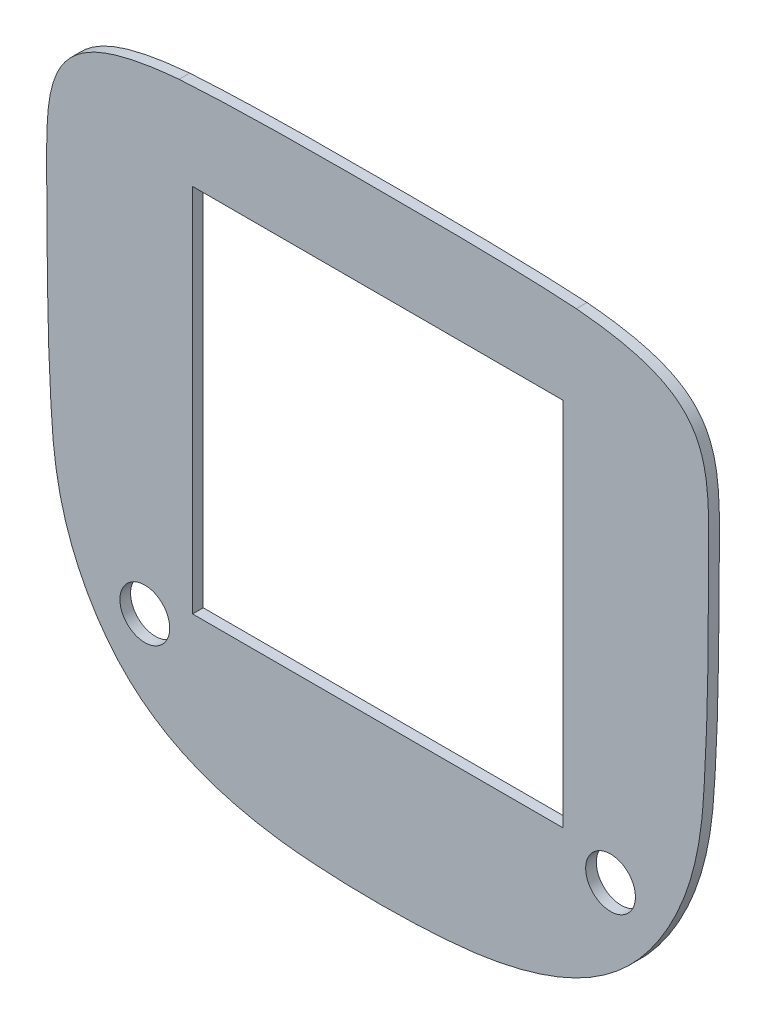
SolidWorks part; units mm, degrees
ref_plane "Front Plane" through (0, 0, 0) normal (0, 0, 1) x (1, 0, 0)
ref_plane "Top Plane" through (0, 0, 0) normal (0, 1, 0) x (1, 0, 0)
ref_plane "Right Plane" through (0, 0, 0) normal (1, 0, 0) x (0, 0, -1)
ref_plane "Plane1" through (0, 0, 100) normal (0, 0, -1) x (-1, 0, 0)
sketch "Sketch1" plane through (0, 0, 100) normal (0, 0, -1) x (-1, 0, 0)
  line L0 (0, 109.7056) -> (0, -73.1371) construction
  line L2 (-52.07, 79.9412) -> (52.07, 79.9412)
  line L3 (-52.07, 79.9412) -> (-52.07, -24.1988)
  line L4 (-52.07, -24.1988) -> (52.07, -24.1988)
  line L5 (52.07, 79.9412) -> (52.07, -24.1988)
  line L6 (-52.07, 79.9412) -> (52.07, -24.1988) construction
  line L7 (-52.07, -24.1988) -> (52.07, 79.9412) construction
  circle A0 centre (-65.5, -30.8878) radius 7
  circle A1 centre (65.5, -30.8878) radius 7
  spline S0 degree 3 poles (431.5804, 2885.9654) (340.7707, 127.7819) (179.6832, -59.6034) (9.156, -68.4596) (4.5994, -68.5614) (-4.5192, -68.5626) (-9.0812, -68.4622) (-15.9299, -68.1084) (-18.2137, -67.9563) (-163.7651, -55.7203) (-324.0036, 115.5461) (2276.1505, 1823.2174) knots -8.863763 -8.863763 -8.863763 -8.863763 0.25 0.25 0.5 0.5 0.75 0.75 0.875 0.875 8.712653 8.712653 8.712653 8.712653 only from (27.355, -67.0609) to (-27.355, -67.0609)
  spline S1 degree 3 poles (-380.9572, -2850.4105) (-413.6013, 4.6753) (-231.265, 98.3934) (-37.5468, 104.943) (-32.9585, 105.0458) (-23.7809, 105.1902) (-19.1919, 105.2316) (-10.0136, 105.2808) (-5.2092, 105.2889) (-0.4047, 105.2894) (-0.1179, 105.2895) (-0.0476, 105.2895) (2.0953, 105.2894) (4.1642, 105.2881) (8.5976, 105.2806) (10.962, 105.2737) (18.055, 105.2405) (22.7834, 105.2016) (32.2392, 105.0607) (36.9665, 104.959) (231.9135, 98.5111) (424.3413, 5.167) (-68.9115, -2862.1998) knots -5.033027 -5.033027 -5.033027 -5.033027 0.125 0.125 0.25 0.25 0.375 0.375 0.5 0.505859 0.505859 0.507813 0.507813 0.5625 0.5625 0.625 0.625 0.75 0.75 0.875 0.875 5.905743 5.905743 5.905743 5.905743 only from (-55.8659, 104.1312) to (55.8659, 104.1312)
  spline S2 degree 3 poles (-55.8659, 104.1312) (-51.2933, 104.4268) (-46.7138, 104.633) (-37.5468, 104.943) (-32.9585, 105.0458) (-23.7809, 105.1902) (-19.1919, 105.2316) (-10.0136, 105.2808) (-5.2092, 105.2889) (-0.4047, 105.2894) (-0.1179, 105.2895) (-0.0476, 105.2895) (2.0953, 105.2894) (4.1642, 105.2881) (8.5976, 105.2806) (10.962, 105.2737) (18.055, 105.2405) (22.7834, 105.2016) (32.2392, 105.0607) (36.9665, 104.959) (46.4194, 104.6463) (51.1472, 104.4362) (55.8659, 104.1312) knots 0 0 0 0 0.125 0.125 0.25 0.25 0.375 0.375 0.5 0.505859 0.505859 0.507813 0.507813 0.5625 0.5625 0.625 0.625 0.75 0.75 0.875 0.875 1 1 1 1
  spline S3 degree 3 poles (27.355, -67.0609) (22.8108, -67.6157) (18.2617, -67.9867) (9.156, -68.4596) (4.5994, -68.5614) (-4.5192, -68.5626) (-9.0812, -68.4622) (-15.9299, -68.1084) (-18.2137, -67.9563) (-22.7835, -67.5721) (-25.0727, -67.3396) (-27.355, -67.0609) knots 0 0 0 0 0.25 0.25 0.5 0.5 0.75 0.75 0.875 0.875 1 1 1 1
  spline S5 degree 3 poles (167.7953, 3089.1539) (-201.0636, -49.2885) (-54.5587, 119.9031) (65.3699, 102.9931) (67.7267, 102.5852) (71.2329, 101.7869) (72.3966, 101.489) (74.7111, 100.8094) (75.8628, 100.4275) (78.1118, 99.5645) (79.2128, 99.082) (80.8185, 98.2584) (81.3461, 97.9672) (82.3838, 97.347) (82.8958, 97.0168) (84.3811, 95.975) (85.3075, 95.2102) (86.5865, 93.9414) (86.9943, 93.4982) (87.7711, 92.5688) (88.1403, 92.0818) (89.1658, 90.5883) (89.7485, 89.5389) (90.4902, 87.8946) (90.7155, 87.3349) (91.1265, 86.1944) (91.3113, 85.616) (91.8065, 83.8785) (92.0608, 82.7092) (92.467, 80.3557) (92.6189, 79.1716) (92.8517, 76.7929) (92.9326, 75.5984) (93.05, 73.203) (93.0856, 72.0013) (93.127, 69.5995) (93.1345, 68.3986) (93.1287, 65.997) (93.118, 64.7962) (93.0925, 61.1938) (93.0791, 58.7922) (93.037, 51.5874) (93.0085, 46.7842) (92.8583, 32.3749) (92.6764, 22.7684) (92.1153, 10.7733) (91.9863, 8.3749) (91.7612, 4.7807) (91.6815, 3.583) (91.5118, 1.1888) (91.4233, -0.008) (91.0907, -3.5921) (90.7896, -5.974) (90.2002, -9.5338) (89.9806, -10.7181) (89.4952, -13.0663) (89.2291, -14.232) (88.3571, -17.7029) (87.6773, -19.9818) (86.1026, -24.4629) (85.2066, -26.6647) (83.7035, -29.9107) (83.1757, -30.9831) (82.0655, -33.1086) (81.4814, -34.1641) (79.655, -37.2802) (78.3442, -39.2833) (75.52, -43.1277) (74.0056, -44.9683) (71.5576, -47.5886) (70.7123, -48.4386) (68.9597, -50.0892) (68.0499, -50.8916) (63.4108, -54.7198) (59.3665, -57.2358) (53.9772, -59.8326) (52.8825, -60.3244) (50.6611, -61.2553) (49.5364, -61.6936) (46.1427, -62.9261) (43.8466, -63.6419) (39.198, -64.8962) (36.8451, -65.4341) (-120.4609, -96.0897) (-334.6066, 201.6706) (90.4464, -3041.4417) knots -1.519961 -1.519961 -1.519961 -1.519961 0.03125 0.03125 0.0625 0.0625 0.078125 0.078125 0.09375 0.09375 0.109375 0.109375 0.117188 0.117188 0.125 0.125 0.140625 0.140625 0.148437 0.148437 0.15625 0.15625 0.171875 0.171875 0.179687 0.179687 0.1875 0.1875 0.203125 0.203125 0.21875 0.21875 0.234375 0.234375 0.25 0.25 0.265625 0.265625 0.28125 0.28125 0.3125 0.3125 0.375 0.375 0.5 0.5 0.53125 0.53125 0.546875 0.546875 0.5625 0.5625 0.59375 0.59375 0.609375 0.609375 0.625 0.625 0.65625 0.65625 0.6875 0.6875 0.703125 0.703125 0.71875 0.71875 0.75 0.75 0.78125 0.78125 0.796875 0.796875 0.8125 0.8125 0.875 0.875 0.890625 0.890625 0.90625 0.90625 0.9375 0.9375 0.96875 0.96875 3.017976 3.017976 3.017976 3.017976 only from (55.8659, 104.1312) to (27.355, -67.0609)
  spline S12 degree 3 poles (55.8659, 104.1312) (58.2532, 103.9195) (60.6333, 103.6609) (65.3699, 102.9931) (67.7267, 102.5852) (71.2329, 101.7869) (72.3966, 101.489) (74.7111, 100.8094) (75.8628, 100.4275) (78.1118, 99.5645) (79.2128, 99.082) (80.8185, 98.2584) (81.3461, 97.9672) (82.3838, 97.347) (82.8958, 97.0168) (84.3811, 95.975) (85.3075, 95.2102) (86.5865, 93.9414) (86.9943, 93.4982) (87.7711, 92.5688) (88.1403, 92.0818) (89.1658, 90.5883) (89.7485, 89.5389) (90.4902, 87.8946) (90.7155, 87.3349) (91.1265, 86.1944) (91.3113, 85.616) (91.8065, 83.8785) (92.0608, 82.7092) (92.467, 80.3557) (92.6189, 79.1716) (92.8517, 76.7929) (92.9326, 75.5984) (93.05, 73.203) (93.0856, 72.0013) (93.127, 69.5995) (93.1345, 68.3986) (93.1287, 65.997) (93.118, 64.7962) (93.0925, 61.1938) (93.0791, 58.7922) (93.037, 51.5874) (93.0085, 46.7842) (92.8583, 32.3749) (92.6764, 22.7684) (92.1153, 10.7733) (91.9863, 8.3749) (91.7612, 4.7807) (91.6815, 3.583) (91.5118, 1.1888) (91.4233, -0.008) (91.0907, -3.5921) (90.7896, -5.974) (90.2002, -9.5338) (89.9806, -10.7181) (89.4952, -13.0663) (89.2291, -14.232) (88.3571, -17.7029) (87.6773, -19.9818) (86.1026, -24.4629) (85.2066, -26.6647) (83.7035, -29.9107) (83.1757, -30.9831) (82.0655, -33.1086) (81.4814, -34.1641) (79.655, -37.2802) (78.3442, -39.2833) (75.52, -43.1277) (74.0056, -44.9683) (71.5576, -47.5886) (70.7123, -48.4386) (68.9597, -50.0892) (68.0499, -50.8916) (63.4108, -54.7198) (59.3665, -57.2358) (53.9772, -59.8326) (52.8825, -60.3244) (50.6611, -61.2553) (49.5364, -61.6936) (46.1427, -62.9261) (43.8466, -63.6419) (39.198, -64.8962) (36.8451, -65.4341) (32.1195, -66.355) (29.7429, -66.7392) (27.355, -67.0609) knots 0 0 0 0 0.03125 0.03125 0.0625 0.0625 0.078125 0.078125 0.09375 0.09375 0.109375 0.109375 0.117188 0.117188 0.125 0.125 0.140625 0.140625 0.148437 0.148437 0.15625 0.15625 0.171875 0.171875 0.179687 0.179687 0.1875 0.1875 0.203125 0.203125 0.21875 0.21875 0.234375 0.234375 0.25 0.25 0.265625 0.265625 0.28125 0.28125 0.3125 0.3125 0.375 0.375 0.5 0.5 0.53125 0.53125 0.546875 0.546875 0.5625 0.5625 0.59375 0.59375 0.609375 0.609375 0.625 0.625 0.65625 0.65625 0.6875 0.6875 0.703125 0.703125 0.71875 0.71875 0.75 0.75 0.78125 0.78125 0.796875 0.796875 0.8125 0.8125 0.875 0.875 0.890625 0.890625 0.90625 0.90625 0.9375 0.9375 0.96875 0.96875 1 1 1 1
  spline S13 degree 3 poles (-147.1204, -3041.406) (334.335, 236.841) (109.0831, -104.9018) (-42.6847, -63.9555) (-43.8419, -63.619) (-46.1319, -62.9003) (-47.2661, -62.5178) (-50.6334, -61.2957) (-52.8313, -60.3812) (-57.119, -58.3222) (-59.2092, -57.1785) (-62.2512, -55.2647) (-63.2496, -54.5936) (-64.7219, -53.5332) (-65.2094, -53.1701) (-66.1677, -52.4314) (-66.6393, -52.0553) (-68.96, -50.142) (-70.697, -48.5052) (-73.9483, -45.0341) (-75.4628, -43.1999) (-77.5866, -40.3172) (-78.2699, -39.3346) (-79.5898, -37.3276) (-80.2278, -36.3007) (-82.0616, -33.1784) (-83.1722, -31.0532) (-85.183, -26.7204) (-86.0835, -24.513) (-87.6676, -20.0134) (-88.3523, -17.7217) (-89.2307, -14.2259) (-89.4991, -13.0493) (-89.987, -10.6855) (-90.206, -9.5011) (-90.7943, -5.9407) (-91.0947, -3.5577) (-91.4263, 0.029) (-91.5147, 1.2269) (-91.6843, 3.6233) (-91.764, 4.8221) (-91.9888, 8.4197) (-92.1178, 10.8204) (-92.6784, 22.8314) (-92.8595, 32.4481) (-93.0092, 46.8746) (-93.0375, 51.6834) (-93.0797, 58.8965) (-93.0933, 61.3009) (-93.1188, 64.9075) (-93.1296, 66.1097) (-93.1341, 68.5141) (-93.1259, 69.7163) (-93.0826, 72.1206) (-93.0457, 73.3227) (-92.9246, 75.7269) (-92.8411, 76.9308) (-92.6007, 79.3248) (-92.4441, 80.5157) (-92.026, 82.8795) (-91.7644, 84.0525) (-91.2564, 85.7924) (-91.0682, 86.367) (-90.6528, 87.4942) (-90.4251, 88.0482) (-89.6753, 89.6779) (-89.0858, 90.7212) (-88.0451, 92.2106) (-87.6751, 92.6901) (-86.8984, 93.6048) (-86.4904, 94.0418) (-85.2103, 95.2944) (-84.2821, 96.0518) (-82.7914, 97.0857) (-82.2819, 97.4107) (-81.2485, 98.0222) (-80.7234, 98.3094) (-79.1256, 99.1218) (-78.0306, 99.5982) (-75.795, 100.4508) (-74.6518, 100.8282) (-72.3431, 101.5033) (-71.1825, 101.7993) (-67.6864, 102.5926) (-65.337, 102.9983) (54.558, 119.8756) (200.0615, -49.0668) (-153.1811, 3089.6354) knots -1.958243 -1.958243 -1.958243 -1.958243 0.0625 0.0625 0.078125 0.078125 0.09375 0.09375 0.125 0.125 0.15625 0.15625 0.171875 0.171875 0.179688 0.179688 0.1875 0.1875 0.21875 0.21875 0.25 0.25 0.265625 0.265625 0.28125 0.28125 0.3125 0.3125 0.34375 0.34375 0.375 0.375 0.390625 0.390625 0.40625 0.40625 0.4375 0.4375 0.453125 0.453125 0.46875 0.46875 0.5 0.5 0.625 0.625 0.6875 0.6875 0.71875 0.71875 0.734375 0.734375 0.75 0.75 0.765625 0.765625 0.78125 0.78125 0.796875 0.796875 0.8125 0.8125 0.820313 0.820313 0.828125 0.828125 0.84375 0.84375 0.851563 0.851563 0.859375 0.859375 0.875 0.875 0.882813 0.882813 0.890625 0.890625 0.90625 0.90625 0.921875 0.921875 0.9375 0.9375 0.96875 0.96875 2.524827 2.524827 2.524827 2.524827 only from (-27.355, -67.0609) to (-55.8659, 104.1312)
  spline S14 degree 3 poles (-27.355, -67.0609) (-32.1327, -66.4173) (-36.8622, -65.5264) (-42.6847, -63.9555) (-43.8419, -63.619) (-46.1319, -62.9003) (-47.2661, -62.5178) (-50.6334, -61.2957) (-52.8313, -60.3812) (-57.119, -58.3222) (-59.2092, -57.1785) (-62.2512, -55.2647) (-63.2496, -54.5936) (-64.7219, -53.5332) (-65.2094, -53.1701) (-66.1677, -52.4314) (-66.6393, -52.0553) (-68.96, -50.142) (-70.697, -48.5052) (-73.9483, -45.0341) (-75.4628, -43.1999) (-77.5866, -40.3172) (-78.2699, -39.3346) (-79.5898, -37.3276) (-80.2278, -36.3007) (-82.0616, -33.1784) (-83.1722, -31.0532) (-85.183, -26.7204) (-86.0835, -24.513) (-87.6676, -20.0134) (-88.3523, -17.7217) (-89.2307, -14.2259) (-89.4991, -13.0493) (-89.987, -10.6855) (-90.206, -9.5011) (-90.7943, -5.9407) (-91.0947, -3.5577) (-91.4263, 0.029) (-91.5147, 1.2269) (-91.6843, 3.6233) (-91.764, 4.8221) (-91.9888, 8.4197) (-92.1178, 10.8204) (-92.6784, 22.8314) (-92.8595, 32.4481) (-93.0092, 46.8746) (-93.0375, 51.6834) (-93.0797, 58.8965) (-93.0933, 61.3009) (-93.1188, 64.9075) (-93.1296, 66.1097) (-93.1341, 68.5141) (-93.1259, 69.7163) (-93.0826, 72.1206) (-93.0457, 73.3227) (-92.9246, 75.7269) (-92.8411, 76.9308) (-92.6007, 79.3248) (-92.4441, 80.5157) (-92.026, 82.8795) (-91.7644, 84.0525) (-91.2564, 85.7924) (-91.0682, 86.367) (-90.6528, 87.4942) (-90.4251, 88.0482) (-89.6753, 89.6779) (-89.0858, 90.7212) (-88.0451, 92.2106) (-87.6751, 92.6901) (-86.8984, 93.6048) (-86.4904, 94.0418) (-85.2103, 95.2944) (-84.2821, 96.0518) (-82.7914, 97.0857) (-82.2819, 97.4107) (-81.2485, 98.0222) (-80.7234, 98.3094) (-79.1256, 99.1218) (-78.0306, 99.5982) (-75.795, 100.4508) (-74.6518, 100.8282) (-72.3431, 101.5033) (-71.1825, 101.7993) (-67.6864, 102.5926) (-65.337, 102.9983) (-60.6162, 103.6628) (-58.2446, 103.9203) (-55.8659, 104.1312) knots 0 0 0 0 0.0625 0.0625 0.078125 0.078125 0.09375 0.09375 0.125 0.125 0.15625 0.15625 0.171875 0.171875 0.179688 0.179688 0.1875 0.1875 0.21875 0.21875 0.25 0.25 0.265625 0.265625 0.28125 0.28125 0.3125 0.3125 0.34375 0.34375 0.375 0.375 0.390625 0.390625 0.40625 0.40625 0.4375 0.4375 0.453125 0.453125 0.46875 0.46875 0.5 0.5 0.625 0.625 0.6875 0.6875 0.71875 0.71875 0.734375 0.734375 0.75 0.75 0.765625 0.765625 0.78125 0.78125 0.796875 0.796875 0.8125 0.8125 0.820313 0.820313 0.828125 0.828125 0.84375 0.84375 0.851563 0.851563 0.859375 0.859375 0.875 0.875 0.882813 0.882813 0.890625 0.890625 0.90625 0.90625 0.921875 0.921875 0.9375 0.9375 0.96875 0.96875 1 1 1 1
  point P7 (0, 27.8712)
  dimension "D1" = 14
  dimension "D2" = 104.14
  dimension "D3" = 104.14
extrude "Boss-Extrude1" add sketch "Sketch1" along normal blind 3 contours A1 A0 L2 L5 L4 L3 region at (0, -66.0141, 100)
